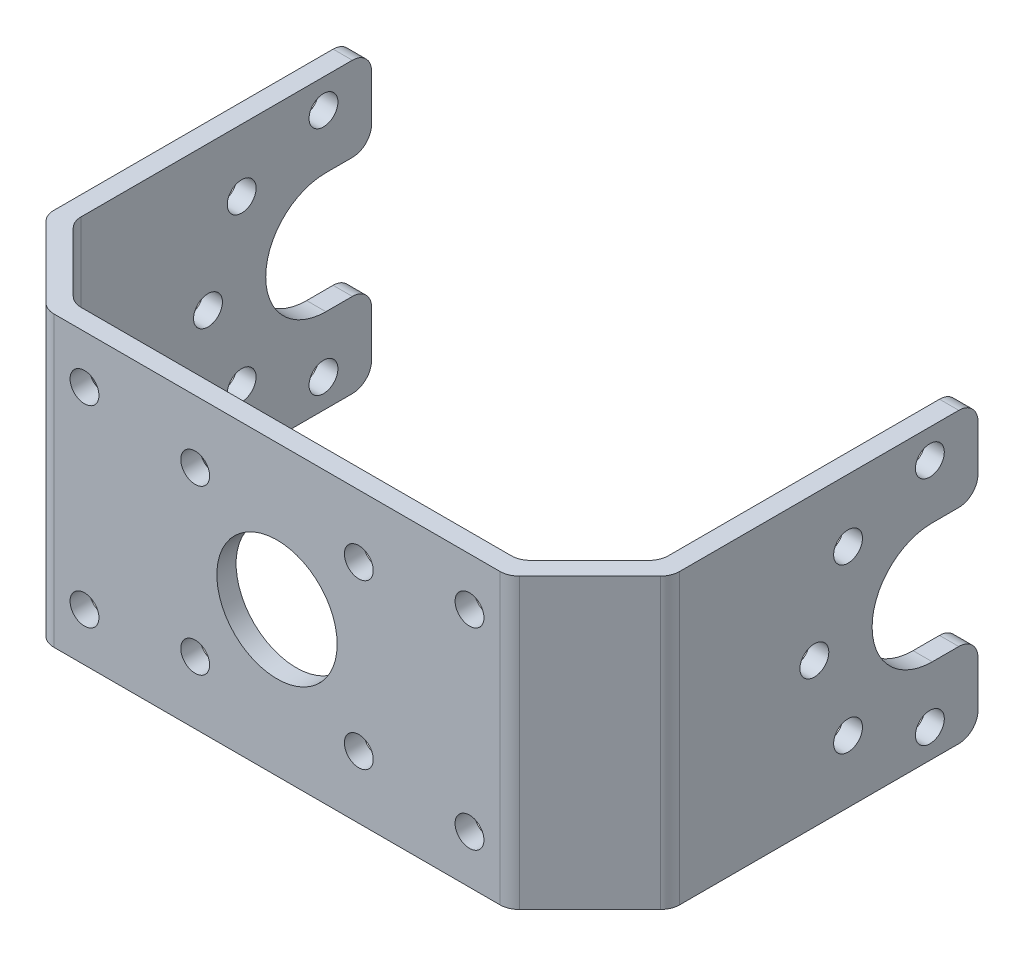
SolidWorks part; units mm, degrees
ref_plane "Front Plane" through (0, 0, 0) normal (0, 0, 1) x (1, 0, 0)
ref_plane "Top Plane" through (0, 0, 0) normal (0, 1, 0) x (1, 0, 0)
ref_plane "Right Plane" through (0, 0, 0) normal (1, 0, 0) x (0, 0, -1)
sketch "Sketch1" plane through (0, 0, 0) normal (0, 1, 0) x (1, 0, 0)
  line L6 (0, -38.3284) -> (23.1716, -38.3284)
  line L7 (0, -38.3284) -> (0, -40.3284)
  line L8 (0, -40.3284) -> (24, -40.3284)
  line L9 (30.5, 0) -> (30.5, -31)
  line L10 (30.5, -31) -> (23.1716, -38.3284)
  line L11 (32.5, 0) -> (32.5, -31.8284)
  line L13 (30.5, 0) -> (32.5, 0)
  line L19 (26.8358, -34.6642) -> (28.25, -36.0784) construction
  line L20 (24, -40.3284) -> (32.5, -31.8284)
  point P10 (0, -38.3284)
  point P31 (28.25, -36.0784)
  dimension "D1" = 30.5
  dimension "D2" = 24
  dimension "D3" = 2
  dimension "D4" = 2
  dimension "D5" = 31
  dimension "D6" = 2
extrude "Boss-Extrude2" add sketch "Sketch1" along normal blind 30
mirror "Mirror1" about plane through (0, 0, 0) normal (1, 0, 0) of "Boss-Extrude2"
sketch "Sketch2" plane through (32.5, 0, 0) normal (1, 0, 0) x (0, 0, -1)
  line L0 (0, 15) -> (-11, 15) construction
  line L1 (0, 30) -> (0, 0) construction
  line L2 (-11, 15) -> (-13.5, 15) construction
  line L3 (-4.75, 21.25) -> (0, 21.25)
  line L4 (-4.75, 8.75) -> (0, 8.75)
  line L5 (0, 21.25) -> (0, 8.75)
  line L6 (-5, 27) -> (-5, 3) construction
  line L7 (-13.5, 15) -> (-17, 15) construction
  line L19 (-13.5, 23.5) -> (-13.5, 6.5) construction
  arc A0 (-4.75, 21.25) -> (-4.75, 8.75) centre (-4.75, 15) ccw
  circle A2 centre (-17, 15) radius 1.5
  circle A3 centre (-5, 3) radius 1.5
  circle A4 centre (-13.5, 6.5) radius 1.5
  circle A5 centre (-13.5, 23.5) radius 1.5
  circle A6 centre (-5, 27) radius 1.5
  point P7 (-11, 15)
  point P23 (-5, 15)
extrude "Cut-Extrude1" cut sketch "Sketch2" against normal through all
sketch "Sketch3" plane through (0, 0, 40.3284) normal (0, 0, 1) x (1, 0, 0)
  line L0 (0, 0) -> (0, 30) construction
  line L1 (-8.5, 6.5) -> (-20, 6.5) construction
  line L2 (-24, 0) -> (24, 0) construction
  line L3 (-8.5, 23.5) -> (-8.5, 6.5) construction
  line L4 (-24, 30) -> (24, 30) construction
  line L5 (0, 15) -> (8.5, 15) construction
  line L6 (0, 15) -> (-8.5, 15) construction
  line L7 (8.5, 23.5) -> (8.5, 6.5) construction
  line L8 (-8.5, 23.5) -> (-20, 23.5) construction
  line L11 (8.5, 23.5) -> (20, 23.5) construction
  line L12 (8.5, 6.5) -> (20, 6.5) construction
  circle A0 centre (0, 15) radius 6.25
  circle A1 centre (8.5, 6.5) radius 1.5
  circle A2 centre (8.5, 23.5) radius 1.5
  circle A7 centre (20, 5) radius 1.5
  circle A8 centre (20, 25) radius 1.5
  circle A9 centre (-20, 5) radius 1.5
  circle A10 centre (-8.5, 6.5) radius 1.5
  circle A11 centre (-20, 25) radius 1.5
  circle A12 centre (-8.5, 23.5) radius 1.5
  point P13 (8.5, 15)
  point P16 (-8.5, 15)
  dimension "D1" = 11.5
  dimension "D2" = 3
  dimension "D3" = 3
  dimension "D4" = 3
  dimension "D5" = 3
  dimension "D7" = 12.5
  dimension "D6" = 17
extrude "Cut-Extrude2" cut sketch "Sketch3" against normal blind 10
fillet "Fillet1" radius 2 16 edges at (-23.1716, 15, 38.3284) (-30.5, 15, 31) (-24, 15, 40.3284) (-32.5, 15, 31.8284) (-31.5, 0, 0) (-31.5, 30, 0) (-31.5, 21.25, 0) (-31.5, 8.75, 0) (31.5, 0, 0) (31.5, 8.75, 0) (31.5, 21.25, 0) (31.5, 30, 0) (30.5, 15, 31) (23.1716, 15, 38.3284) (32.5, 15, 31.8284) (24, 15, 40.3284)
